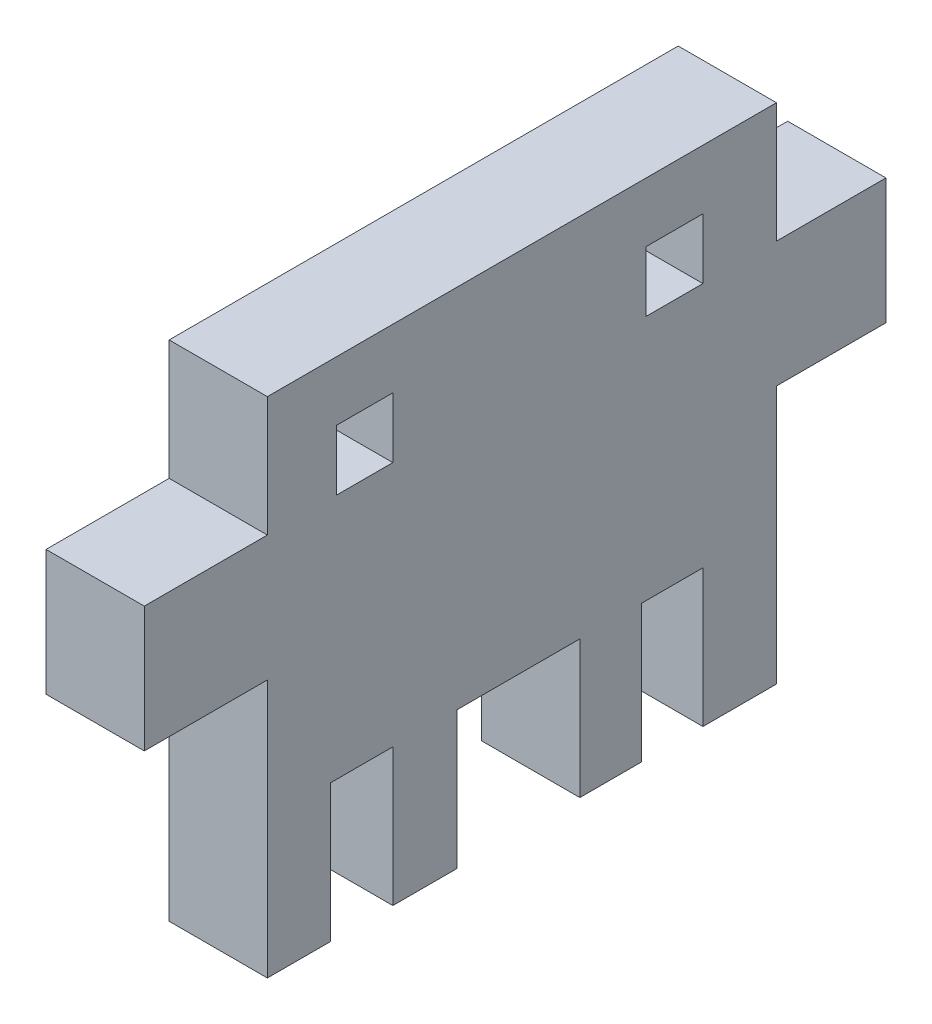
SolidWorks part; units mm, degrees
ref_plane "前视基准面" through (0, 0, 0) normal (0, 0, 1) x (1, 0, 0)
ref_plane "上视基准面" through (0, 0, 0) normal (0, 1, 0) x (1, 0, 0)
ref_plane "右视基准面" through (0, 0, 0) normal (1, 0, 0) x (0, 0, -1)
sketch "草图2" plane through (0, 0, 0) normal (1, 0, 0) x (0, 0, -1)
  line L0 (60.0749, 311.6519) -> (210.0749, 311.6519) construction
  line L1 (109.9667, 259.081) -> (122.9845, 259.081)
  line L2 (84.4193, 361.596) -> (188.0734, 361.596)
  line L3 (84.4193, 361.596) -> (84.4193, 337.1877)
  line L4 (84.4193, 259.081) -> (97.2744, 259.081)
  line L5 (188.0734, 361.596) -> (188.0734, 337.1877)
  line L6 (59.3601, 337.1877) -> (84.4193, 337.1877)
  line L7 (59.3601, 337.1877) -> (59.3601, 311.6403)
  line L8 (59.3601, 311.6403) -> (84.4193, 311.6403)
  line L9 (210.3664, 337.1877) -> (210.3664, 311.6403)
  line L10 (97.2744, 287.0692) -> (109.9667, 287.0692)
  line L11 (97.2744, 287.0692) -> (97.2744, 259.081)
  line L13 (109.9667, 287.0692) -> (109.9667, 259.081)
  line L14 (122.9845, 287.0692) -> (148.0438, 287.0692)
  line L15 (122.9845, 287.0692) -> (122.9845, 259.081)
  line L17 (148.0438, 287.0692) -> (148.0438, 259.081)
  line L18 (160.5734, 287.0692) -> (173.103, 287.0692)
  line L19 (160.5734, 287.0692) -> (160.5734, 259.081)
  line L21 (173.103, 287.0692) -> (173.103, 259.081)
  line L22 (148.0438, 259.081) -> (160.5734, 259.081)
  line L23 (173.103, 259.081) -> (188.0734, 259.081)
  line L24 (188.0734, 311.6403) -> (210.3664, 311.6403)
  line L25 (84.4193, 311.6403) -> (84.4193, 259.081)
  line L26 (188.0734, 337.1877) -> (210.3664, 337.1877)
  line L27 (188.0734, 311.6403) -> (188.0734, 259.081)
  line L33 (98.5115, 349.4962) -> (109.9667, 349.4962)
  line L34 (98.5115, 349.4962) -> (98.5115, 337.1877)
  line L35 (98.5115, 337.1877) -> (109.9667, 337.1877)
  line L36 (109.9667, 349.4962) -> (109.9667, 337.1877)
  line L37 (161.4925, 349.4962) -> (173.103, 349.4962)
  line L38 (161.4925, 349.4962) -> (161.4925, 337.1877)
  line L39 (161.4925, 337.1877) -> (173.103, 337.1877)
  line L40 (173.103, 349.4962) -> (173.103, 337.1877)
  dimension "D1" = 150
extrude "凸台-拉伸1" add sketch "草图2" along normal blind 20
